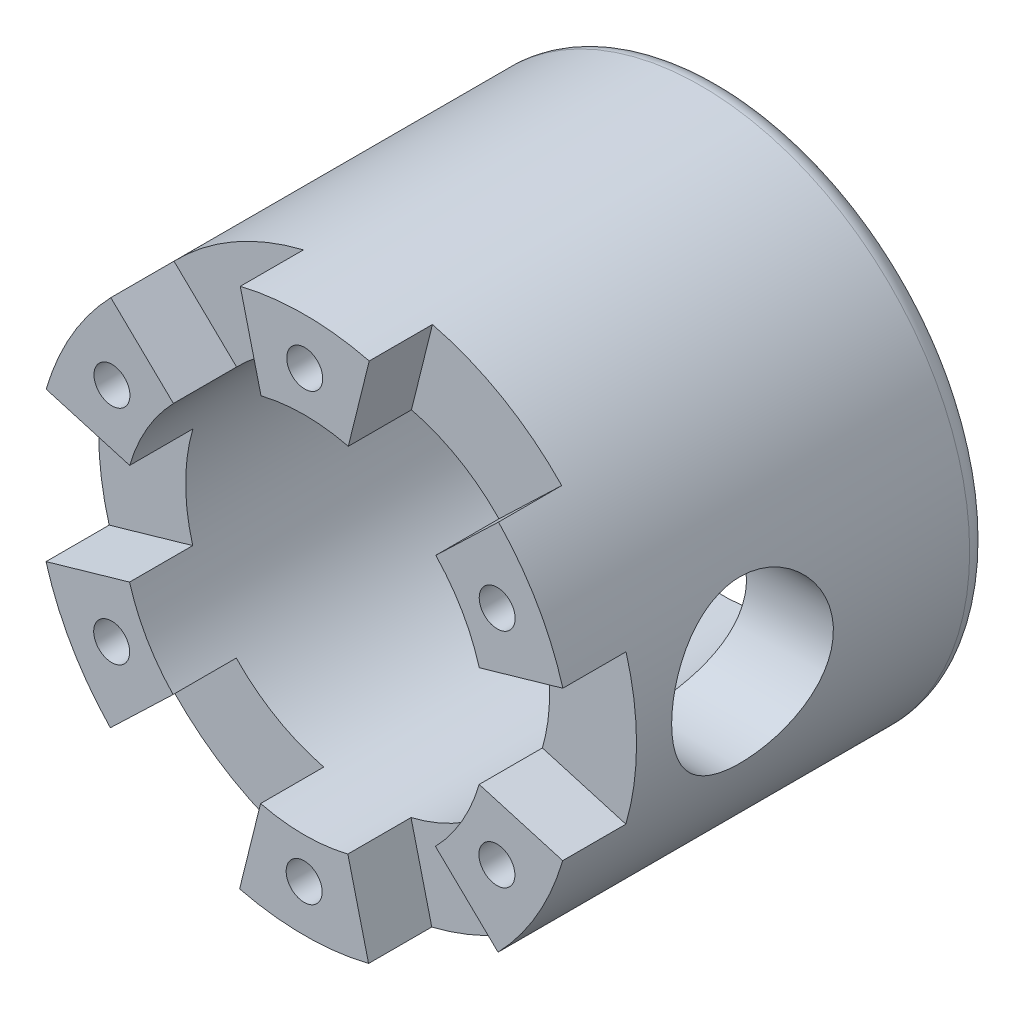
SolidWorks part; units mm, degrees
note: The reader was unsure of these and kept them because the rebuilt part matched: shared geometry of "Sketch11<4>".
material "ABS PC"
ref_plane "Front Plane" through (0, 0, 0) normal (0, 0, 1) x (1, 0, 0)
ref_plane "Top Plane" through (0, 0, 0) normal (0, 1, 0) x (1, 0, 0)
ref_plane "Right Plane" through (0, 0, 0) normal (1, 0, 0) x (0, 0, -1)
sketch "Sketch1" plane through (0, 0, 0) normal (0, 0, 1) x (1, 0, 0)
  circle A0 centre (0, 0) radius 16.891
  dimension "D1" = 33.782
extrude "Boss-Extrude1" add sketch "Sketch1" along normal blind 26.162
sketch "Sketch9" plane through (0, 0, 0) normal (0, 0, -1) x (-1, 0, 0)
  line L0 (0, 0) -> (7.874, 0) construction
  line L1 (0, 0) -> (0, 7.874) construction
  line L2 (7.874, -7.874) -> (7.874, 7.874)
  line L3 (7.874, 7.874) -> (-7.874, 7.874)
  line L4 (-7.874, -7.874) -> (-7.874, 7.874)
  line L5 (7.874, -7.874) -> (-7.874, -7.874)
  circle A0 centre (0, 0) radius 9.525
  point P8 (-7.874, 0)
  dimension "D3" = 19.05
  dimension "D1" = 7.874
  dimension "D2" = 7.874
extrude "Cut-Extrude6" cut sketch "Sketch9" against normal through all contours A0 | L5 A0 | L4 A0 | L3 A0 | L2 A0
sketch "Sketch10" plane through (0, 0, 0) normal (0, 0, -1) x (-1, 0, 0)
  line L0 (-16.891, 0) -> (-11.43, 0) construction
  circle A0 centre (0, 0) radius 16.891
  circle A1 centre (0, 0) radius 11.43
  dimension "D1" = 22.86
  dimension "D2" = 33.782
extrude "Boss-Extrude2" add sketch "Sketch10" against normal blind 19.05
sketch "Sketch11" plane through (0, 0, 26.162) normal (0, 0, 1) x (1, 0, 0)
  line L0 (-10.9842, -3.1612) -> (-16.2322, -4.6715)
  line L1 (-10.9762, 3.1888) -> (-16.2203, 4.7124)
  line L2 (-10.9762, 3.1888) -> (0, 0) construction
  line L3 (-10.9842, -3.1612) -> (0, 0) construction
  line L4 (-10.9762, 3.1888) -> (0, 0)
  line L5 (0, 0) -> (-10.9842, -3.1612)
  line L6 (0, 0) -> (-12.0896, 7.0002) construction
  line L7 (0, 0) -> (-16.9257, 0.0213) construction
  arc A2 (-10.9842, -3.1612) -> (-10.9762, 3.1888) centre (4.7575, -0.006) cw
  arc A3 (-16.2203, 4.7124) -> (-16.2322, -4.6715) centre (-0.84, 0.0011) ccw
  circle A4 centre (0, 0) radius 11.43
  circle M7 centre (0, 0) radius 16.891
  circle M33 centre (0, 0) radius 9.525
  dimension "D1" = 6.35
  dimension "D2" = 30
  dimension "D3" = 13.97
extrude "Cut-Extrude7" cut sketch "Sketch11" against normal through all contours L5 A4 L4 M33 | A2 L5 L4 M33 | A2 A4
extrude "Cut-Extrude8" cut sketch "Sketch11<4>" against normal blind 3.9688 contours A4 L1 L0 M7
sketch "Sketch11<4>" plane through (0, 0, 26.162) normal (0, 0, 1) x (1, 0, 0) same geometry as "Sketch11"
hole_wizard "CSK for #2 Flat Head Machine Screw1" positions "Sketch13" profile "Sketch14" countersink size "#2" standard "ANSI Inch" end condition through all
sketch "Sketch13" plane through (0, 0, 0) normal (0, 0, -1) x (-1, 0, 0)
  point P0 (12.0896, 7.0002)
sketch "Sketch14" plane through (-12.0896, 7.0002, 0) normal (1, 0, 0) x (0, 1, 0)
  line L0 (0, 0) -> (0, 26.162)
  line L1 (0, 26.162) -> (1.1303, 26.162)
  line L2 (1.1303, 26.162) -> (1.1303, 1.2126)
  line L3 (1.1303, 1.2126) -> (2.1844, 0)
  line L5 (2.1844, 0) -> (0, 0)
  line L6 (-1.1303, 1.2126) -> (-2.1844, 0) construction
  line L11 (0, -6.35) -> (0, 107.95) construction
  dimension "Thru Hole Dia." = 2.2606
  dimension "Thru Hole Depth" = 26.162
  dimension "Near C'Sink Dia." = 4.3688
  dimension "Near C'Sink Angle" = 82
pattern_circular "CirPattern1" count 6 over 360 about axis through (0, 0, 0) along (0, 0, 1) of "Cut-Extrude8", "CSK for #2 Flat Head Machine Screw1"
hole_wizard "1/2 (0.4) Diameter Hole1" positions "3DSketch1" profile "Sketch15" hole size "1/2" standard "ANSI Inch"
sketch3d "3DSketch1"
  line L0 (16.2322, 4.6715, 22.1933) -> (16.2203, -4.7124, 22.1933) construction
  line L2 (16.2262, -0.0204, 22.1933) -> (16.891, -0.0212, 22.1933) construction
  line L4 (16.891, -0.0212, 22.1933) -> (16.891, -0.0212, 0) construction
  line L6 (12.1072, 6.9698, 0) -> (12.0896, -7.0002, 0) construction
  line L7 (12.1072, 6.9698, 0) -> (12.1072, 6.9698, 1.2126) construction
  line L8 (12.0896, -7.0002, 0) -> (12.0896, -7.0002, 1.2126) construction
  line L11 (12.0984, -0.0152, 0) -> (16.891, -0.0212, 0) construction
  circle A1 centre (0, 0, 0) radius 16.891 construction
  arc A2 (16.2203, -4.7124, 22.1933) -> (16.2322, 4.6715, 22.1933) centre (0, 0, 22.1933) ccw construction
  point P0 (16.891, -0.0212, 14.9081)
  point P19 (0, 0, 16.891)
  point P35 (0, 0, 39.0843)
sketch "Sketch15" plane through (16.891, -0.0212, 14.9081) normal (0, 0, 1) x (0.0013, 1, 0)
  line L0 (0, 0) -> (0, 15.7524)
  line L1 (0, 15.7524) -> (5.08, 12.7)
  line L2 (5.08, 12.7) -> (5.08, 0)
  line L5 (5.08, 0) -> (0, 0)
  line L10 (0, 15.7524) -> (-5.08, 12.7) construction
  line L11 (0, -6.35) -> (0, 107.95) construction
  dimension "Hole Dia." = 10.16
  dimension "Hole Depth" = 12.7
  dimension "Drill Angle" = 118
fillet "Fillet1" radius 1.27 1 edges at (16.891, 0, 0)
